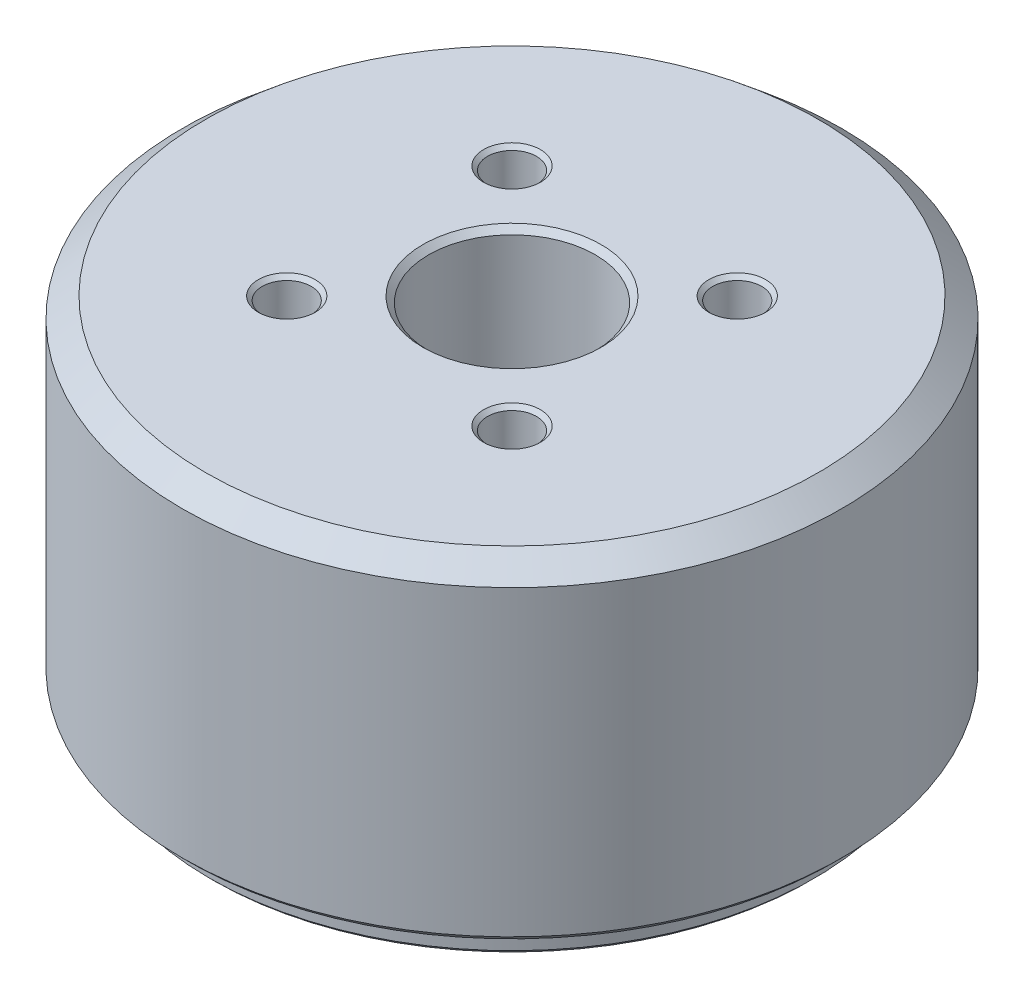
SolidWorks part; units mm, degrees
ref_plane "前视基准面" through (0, 0, 0) normal (0, 0, 1) x (1, 0, 0)
ref_plane "上视基准面" through (0, 0, 0) normal (0, 1, 0) x (1, 0, 0)
ref_plane "右视基准面" through (0, 0, 0) normal (1, 0, 0) x (0, 0, -1)
sketch "草图1" plane through (0, 0, 0) normal (0, 1, 0) x (1, 0, 0)
  circle A0 centre (0, 0) radius 16.825
  circle A1 centre (0, 0) radius 4.25
  dimension "D1" = 33.65
  dimension "D2" = 8.5
extrude "凸台-拉伸1" add sketch "草图1" along normal blind 18.24
sketch "草图2" plane through (0, 0, 0) normal (0, -1, 0) x (1, 0, 0)
  circle A0 centre (0, 0) radius 4.25 construction
  circle A1 centre (0, 0) radius 4.25
  circle A2 centre (0, 0) radius 6.025
  dimension "D1" = 12.05
extrude "凸台-拉伸2" add sketch "草图2" along normal blind 1.76
sketch "草图3" plane through (0, 0, 0) normal (0, -1, 0) x (1, 0, 0)
  line L0 (0, 0) -> (17.7473, 17.7473) construction
  line L1 (0, 0) -> (15.0157, -15.0157) construction
  circle A0 centre (-7.75, 7.75) radius 1.25
  circle A2 centre (-7.75, -7.75) radius 1.25
  circle A3 centre (7.75, 7.75) radius 1.25
  circle A4 centre (7.75, -7.75) radius 1.25
  point P11 (-8.5353, 8.5353)
  point P12 (0, 0)
  point P13 (0, 0)
  point P15 (-8.8024, 6.025)
  point P17 (0, 0)
  point P18 (0, 0)
  point P19 (0, 0)
  point P20 (0, 0)
  point P21 (7.75, 7.75)
  dimension "D1" = 2.5
  dimension "D2" = 2.5
  dimension "D3" = 2.5
  dimension "D4" = 2.5
  dimension "D5" = 15.5
  dimension "D6" = 15.5
extrude "切除-拉伸1" cut sketch "草图3" against normal blind 4.5
sketch "草图4" plane through (0, 18.24, 0) normal (0, 1, 0) x (1, 0, 0)
  line L0 (0, 0) -> (0.5329, 0.5329) construction
  line L1 (0, 0) -> (0.5073, -0.5073) construction
  circle A0 centre (0, 0) radius 4.25 construction
  circle A1 centre (0, 0) radius 4.25 construction
  circle A2 centre (-5.75, 5.75) radius 1.25
  circle A3 centre (-5.75, -5.75) radius 1.25
  circle A4 centre (5.75, -5.75) radius 1.25
  circle A5 centre (5.75, 5.75) radius 1.25
  point P15 (0, 0)
  point P16 (0, 0)
  point P17 (0, 0)
  point P18 (0, 0)
  point P19 (5.6353, -5.6353)
  dimension "D1" = 2.5
  dimension "D2" = 2.5
  dimension "D3" = 2.5
  dimension "D4" = 2.5
  dimension "D5" = 11.5
extrude "切除-拉伸2" cut sketch "草图4" against normal blind 2.5
sketch "草图5" plane through (0, 0, 0) normal (0, -1, 0) x (1, 0, 0)
  circle A0 centre (0, 0) radius 15.425
  circle A1 centre (0, 0) radius 16.825 construction
  circle A2 centre (0, 0) radius 16.825
  dimension "D1" = 30.85
extrude "切除-拉伸3" cut sketch "草图5" against normal blind 1.5
sketch "草图6" plane through (0, -1.76, 0) normal (0, -1, 0) x (1, 0, 0)
  circle A0 centre (0, 0) radius 5.79
  circle A1 centre (0, 0) radius 6.025 construction
  circle A2 centre (0, 0) radius 6.025
  dimension "D1" = 11.58
extrude "切除-拉伸4" cut sketch "草图6" against normal blind 1.26
sketch "草图7" plane through (0, 0, 0) normal (0, -1, 0) x (1, 0, 0)
  line L0 (0, 6.025) -> (0, 11.525) construction
  line L1 (-1.025, 11.525) -> (1.025, 11.525) construction
  line L2 (-1.025, 12.525) -> (1.025, 12.525)
  line L3 (-1.025, 10.525) -> (1.025, 10.525)
  circle A2 centre (0, 0) radius 6.025 construction
  circle A3 centre (0, 0) radius 6.025 construction
  arc A4 (-1.025, 12.525) -> (-1.025, 10.525) centre (-1.025, 11.525) ccw
  arc A5 (1.025, 10.525) -> (1.025, 12.525) centre (1.025, 11.525) ccw
  point P12 (0, 11.525)
  point P17 (0, 0)
  dimension "D3" = 4.05
  dimension "D1" = 5.5
  dimension "D2" = 2
extrude "切除-拉伸5" cut sketch "草图7" against normal blind 0.5
chamfer "倒角1" distance 1 angle 50 1 edges at (0, 18.24, 16.825) first distance on face at (0, 18.24, 16.825)
chamfer "倒角2" distance 0.3 angle 45 1 edges at (0, 1.5, -16.825)
chamfer "倒角3" distance 0.2 angle 45 1 edges at (0, 0, -15.425)
chamfer "倒角4" distance 0.2 angle 45 4 edges at (-7.75, 0, -9) (7.75, 0, -9) (7.75, 0, 6.5) (-7.75, 0, 6.5)
chamfer "倒角5" distance 0.2 angle 45 4 edges at (-5.75, 18.24, -4.5) (5.75, 18.24, -4.5) (5.75, 18.24, 7) (-5.75, 18.24, 7)
chamfer "倒角6" distance 0.3 angle 45 1 edges at (0, 18.24, 4.25)
fillet "圆角1" radius 0.3 1 edges at (0, -1.76, -4.25)
fillet "圆角2" radius 0.4 1 edges at (0, -1.76, -5.79)
